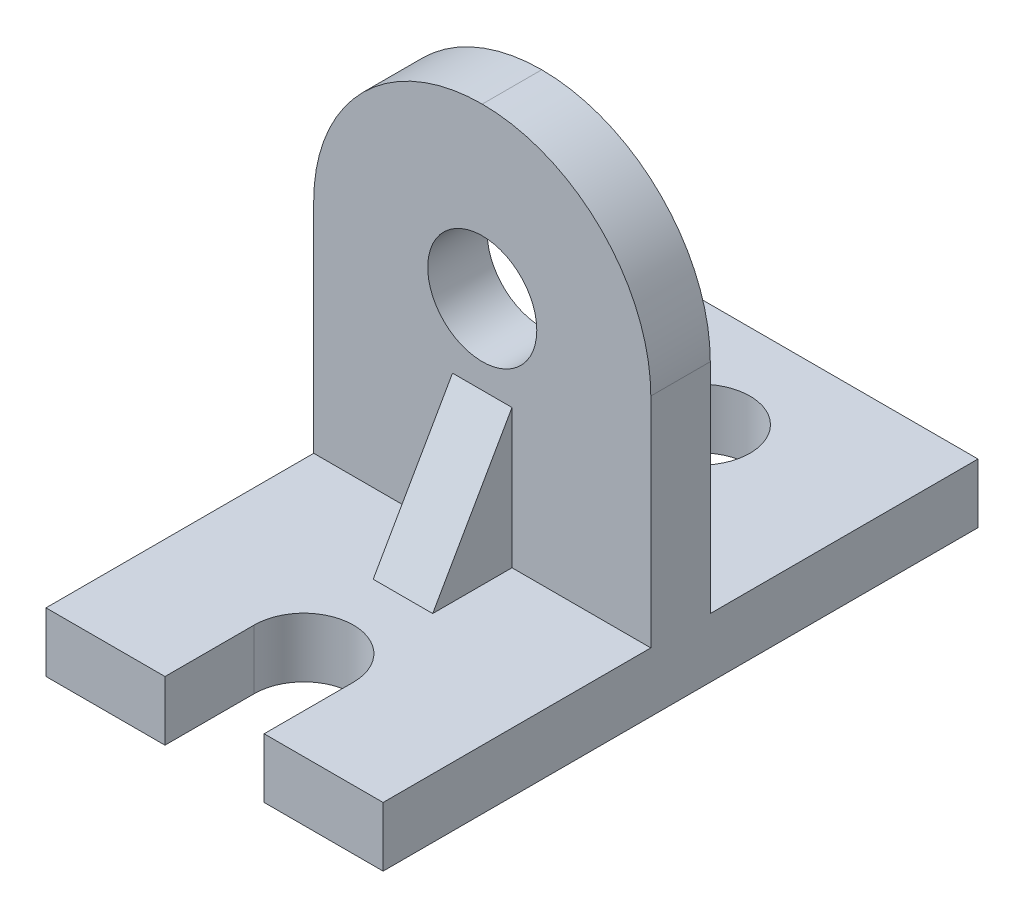
SolidWorks part; units mm, degrees
ref_plane "Спереди" through (0, 0, 0) normal (0, 0, 1) x (1, 0, 0)
ref_plane "Сверху" through (0, 0, 0) normal (0, 1, 0) x (1, 0, 0)
ref_plane "Справа" through (0, 0, 0) normal (1, 0, 0) x (0, 0, -1)
sketch "Эскиз1" plane through (0, 0, 0) normal (1, 0, 0) x (0, 0, -1)
  line L0 (-11, -19.5) -> (-3, -5.5)
  line L1 (-3, -19.5) -> (3, -19.5)
  line L2 (-3, -19.5) -> (-3, 19.5)
  line L3 (-3, 19.5) -> (3, 19.5)
  line L4 (3, -19.5) -> (3, 19.5)
  line L5 (-3, -19.5) -> (3, 19.5) construction
  line L6 (-3, 19.5) -> (3, -19.5) construction
  line L7 (-30, -25.5) -> (30, -25.5)
  line L8 (-30, -25.5) -> (-30, -19.5)
  line L9 (-30, -19.5) -> (30, -19.5)
  line L10 (30, -25.5) -> (30, -19.5)
  line L11 (-30, -25.5) -> (30, -19.5) construction
  line L12 (-30, -19.5) -> (30, -25.5) construction
  line L13 (3, -5.5) -> (11, -19.5)
  point P0 (0, 0)
  point P6 (0, -22.5)
  dimension "D1" = 60
  dimension "D2" = 6
  dimension "D3" = 45
  dimension "D4" = 8
  dimension "D5" = 8
  dimension "D6" = 14
extrude "Бобышка-Вытянуть1" add sketch "Эскиз1" along normal blind 17 and the other way blind 17 contours L1 L4 L3 L2 | L7 L10 L9 L1 L8 region at (0, -22.5, 0) region at (0, 0, 0)
fillet "Скругление1" radius 17 2 edges at (-17, 19.5, 0) (17, 19.5, 0)
sketch "Эскиз2" plane through (0, 0, 3) normal (0, 0, 1) x (1, 0, 0)
  circle A0 centre (0, 2.5) radius 5.5
  dimension "D1" = 11
extrude "Вырез-Вытянуть1" cut sketch "Эскиз2" against normal through all
extrude "Бобышка-Вытянуть2" add sketch "Эскиз1<3>" along normal blind 3 and the other way blind 3 contours L0 L9 L2 | L13 L4 L9 region at (0, -14.8333, 5.6667) region at (0, -14.8333, -5.6667)
sketch "Эскиз1<3>" plane through (0, 0, 0) normal (1, 0, 0) x (0, 0, -1) same geometry as "Эскиз1"
sketch "Эскиз3" plane through (0, -19.5, 0) normal (0, 1, 0) x (1, 0, 0)
  line L0 (-5, -21) -> (-5, -30)
  line L1 (-17, -30) -> (17, -30) construction
  line L2 (-5, -30) -> (5, -30)
  line L3 (5, -30) -> (5, -21)
  line L4 (-17, 30) -> (17, 30) construction
  circle A0 centre (0, -21) radius 5
  circle A1 centre (0, 19) radius 5
  line M4 (-17, -30) -> (17, -30)
  dimension "D1" = 10
  dimension "D3" = 11
  dimension "D2" = 9
extrude "Вырез-Вытянуть2" cut sketch "Эскиз3" against normal through all contours A1 | A0 | A0 L0 L3 M4 region at (0, -19.5, 27.3407) region at (0, -19.5, 21) region at (0, -19.5, -19)
